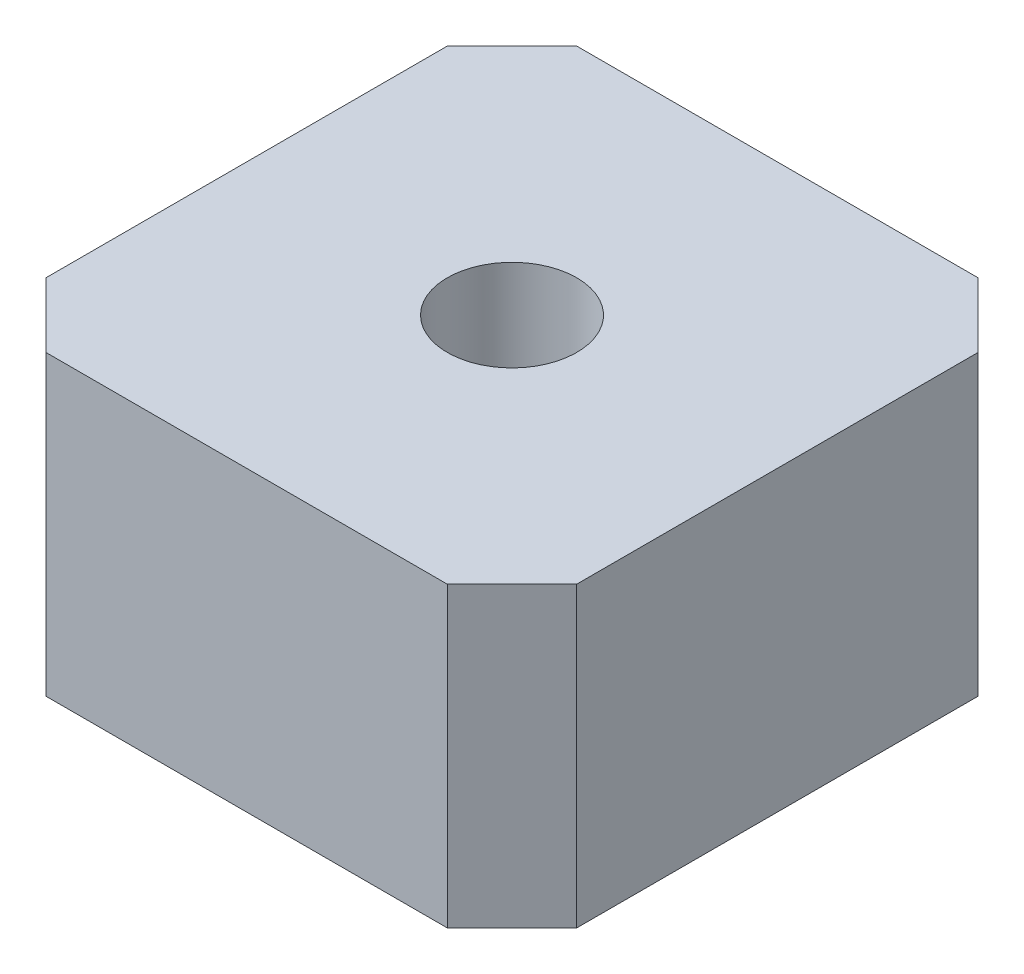
SolidWorks part; units mm, degrees
ref_plane "Front Plane" through (0, 0, 0) normal (0, 0, 1) x (1, 0, 0)
ref_plane "Top Plane" through (0, 0, 0) normal (0, 1, 0) x (1, 0, 0)
ref_plane "Right Plane" through (0, 0, 0) normal (1, 0, 0) x (0, 0, -1)
sketch "Sketch1" plane through (0, 0, 0) normal (0, 1, 0) x (1, 0, 0)
  line L1 (-20.5, -20.5) -> (20.5, -20.5)
  line L2 (-20.5, -20.5) -> (-20.5, 20.5)
  line L3 (-20.5, 20.5) -> (20.5, 20.5)
  line L4 (20.5, -20.5) -> (20.5, 20.5)
  line L5 (-20.5, -20.5) -> (20.5, 20.5) construction
  line L6 (-20.5, 20.5) -> (20.5, -20.5) construction
  point P0 (0, 0)
  dimension "D1" = 41
  dimension "D2" = 41
extrude "Boss-Extrude1" add sketch "Sketch1" along normal blind 23
chamfer "Chamfer1" distance 5 angle 45 4 edges at (20.5, 11.5, 20.5) (20.5, 11.5, -20.5) (-20.5, 11.5, 20.5) (-20.5, 11.5, -20.5)
sketch "Sketch2" plane through (0, 0, 0) normal (0, -1, 0) x (1, 0, 0)
  circle A0 centre (0, 0) radius 5
  dimension "D1" = 10
extrude "Cut-Extrude1" cut sketch "Sketch2" against normal through all
